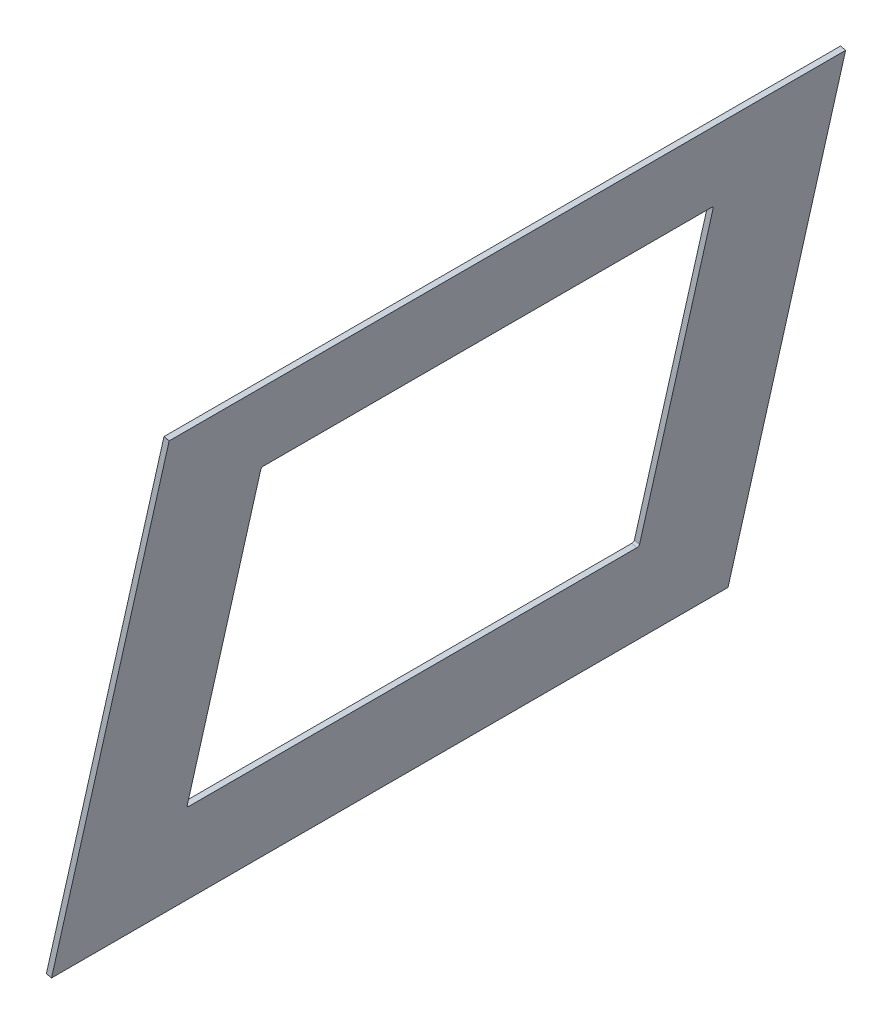
SolidWorks part; units mm, degrees
material "Pine"
ref_plane "Front Plane" through (0, 0, 0) normal (0, 0, 1) x (1, 0, 0)
ref_plane "Top Plane" through (0, 0, 0) normal (0, 1, 0) x (1, 0, 0)
ref_plane "Right Plane" through (0, 0, 0) normal (1, 0, 0) x (0, 0, -1)
sketch "Sketch2" plane through (0, 0, 0) normal (0, 0, 1) x (1, 0, 0)
  line L0 (-108.5345, -3.9032) -> (-108.5345, 1464.0363)
  line L1 (-603.0613, 1609.6249) -> (-744.3883, 980.0776)
  line L2 (-870.5345, -3.9032) -> (-870.5345, 625.8363)
  line L3 (-972.1345, 737.9573) -> (-972.1345, 834.2968)
  line L4 (-768.9345, 834.2968) -> (-768.9345, 986.6968)
  line L5 (-972.1345, 834.2968) -> (-768.9345, 834.2968)
  line L6 (-528.0858, 1843.9468) -> (-737.1845, 1843.9468)
  line L7 (-968.4148, 728.977) -> (-874.2542, 634.8165)
  line L8 (-737.1845, 1672.0154) -> (-737.1845, 1762.6932)
  line L9 (-520.195, 1875.6968) -> (-756.2345, 1875.6968)
  line L10 (-112.2542, 1473.0165) -> (-511.2148, 1871.977)
  line L11 (-737.1845, 1692.941) -> (-241.631, 1467.6894)
  line L12 (-596.8655, 1608.234) -> (-738.1925, 978.6867)
  line L13 (-763.9746, 985.3593) -> (-224.4471, 839.8687)
  line L14 (-761.4898, 1669.1128) -> (-638.6318, 1613.2683)
  line L15 (-631.4955, 1598.9249) -> (-768.9345, 986.6968)
  line L16 (-768.9345, 1680.6745) -> (-768.9345, 1862.9968)
  line L17 (-737.1845, 1780.4468) -> (-737.1845, 1843.9468)
  line L18 (-737.1845, 1692.941) -> (-737.1845, 1843.9468) construction
  line L19 (-737.1845, 1692.941) -> (-737.1845, 1762.6932) construction
  line L20 (-838.7845, -3.9032) -> (-838.7845, 834.2968)
  line L21 (-745.0674, 1675.5986) -> (-249.5139, 1450.347) construction
  line L22 (-140.2845, -3.9032) -> (-140.2845, 1456.1455)
  line L23 (-140.2845, 1456.1455) -> (-528.0858, 1843.9468)
  line L24 (-537.8111, 1581.3911) -> (-673.6845, 976.1369)
  line L25 (-768.9345, 966.9663) -> (-229.407, 821.4757)
  line L26 (-737.1845, 1672.0154) -> (-203.7845, 1429.5608)
  line L27 (-528.0858, 1843.9468) -> (-554.3883, 1780.4468)
  line L28 (-140.2845, 1456.1455) -> (-203.7845, 1429.8429)
  line L29 (-775.2845, -3.9032) -> (-775.2845, 834.2968)
  line L30 (-773.8944, 968.3038) -> (-229.407, 821.4757) construction
  line L31 (-203.7845, -3.9032) -> (-203.7845, 1429.8429)
  line L32 (-203.7845, 1429.8429) -> (-554.3883, 1780.4468)
  line L33 (-554.3883, 1780.4468) -> (-737.1845, 1780.4468)
  line L34 (-768.9345, 966.9663) -> (-763.9746, 985.3593)
  line L35 (-737.1845, 1762.6932) -> (-369.5099, 1595.5683)
  line L36 (-673.6845, 1733.8295) -> (-599.2171, 1699.9807) construction
  line L37 (-737.1845, 1692.941) -> (-625.4936, 1642.1724) construction
  line L38 (-538.5586, 1578.0615) -> (-673.6845, 976.1369) construction
  line L39 (-600.5166, 1591.9704) -> (-737.1845, 983.1768) construction
  line L40 (-554.3883, 1780.4468) -> (-673.6845, 1780.4468) construction
  line L41 (-203.7845, 91.3468) -> (-203.7845, 1429.8429) construction
  line L42 (-140.2845, 27.8468) -> (-140.2845, 1456.1455) construction
  line L43 (-775.2845, 91.3468) -> (-775.2845, 625.8363) construction
  line L44 (-838.7845, 27.8468) -> (-838.7845, 625.8363) construction
  line L45 (-203.7845, 91.3468) -> (-775.2845, 91.3468) construction
  line L46 (-140.2845, 27.8468) -> (-838.7845, 27.8468) construction
  line L47 (-940.3845, 745.8481) -> (-851.8036, 657.2672) construction
  line L48 (-843.7807, 739.0468) -> (-806.9023, 702.1685) construction
  line L49 (-843.7807, 739.0468) -> (-673.6845, 739.0468) construction
  line L50 (-940.3845, 802.5468) -> (-737.1845, 802.5468) construction
  line L51 (-940.3845, 745.8481) -> (-940.3845, 802.5468) construction
  line L52 (-843.7807, 739.0468) -> (-843.7807, 739.0468) construction
  line L53 (-673.6845, 1733.8295) -> (-673.6845, 1780.4468) construction
  line L54 (-756.2345, 1692.941) -> (-756.2345, 1792.2779) construction
  line L55 (-756.2345, 1792.2779) -> (-361.627, 1612.9108) construction
  line L56 (-673.6845, 739.0468) -> (-673.6845, 976.1369) construction
  line L57 (-737.1845, 802.5468) -> (-737.1845, 983.1768) construction
  line L58 (-768.9345, 986.6968) -> (-224.4471, 839.8687) construction
  line L59 (-224.4471, 839.8687) -> (-229.407, 821.4757)
  line L60 (-596.8655, 1608.234) -> (-603.0613, 1609.6249)
  line L61 (-603.0613, 1609.6249) -> (-743.3803, 984.5677) construction
  line L62 (-596.8655, 1608.234) -> (-737.1845, 983.1768) construction
  line L63 (-108.5345, -3.9032) -> (-248.0476, -3.9032)
  line L64 (-744.3883, 980.0776) -> (-738.1925, 978.6867)
  line L68 (-108.5345, -3.9032) -> (-870.5345, -3.9032) construction
  line L69 (-108.5345, -3.9032) -> (-870.5345, -3.9032)
  line L72 (-108.5345, 34.1968) -> (-870.5345, 34.1968)
  arc A0 (-108.5345, 1464.0363) -> (-112.2542, 1473.0165) centre (-121.2345, 1464.0363) ccw
  arc A1 (-511.2148, 1871.977) -> (-520.195, 1875.6968) centre (-520.195, 1862.9968) ccw
  arc A2 (-768.9345, 1862.9968) -> (-756.2345, 1875.6968) centre (-756.2345, 1862.9968) cw
  arc A3 (-768.9345, 1680.6745) -> (-761.4898, 1669.1128) centre (-756.2345, 1680.6745) ccw
  arc A4 (-631.4955, 1598.9249) -> (-638.6318, 1613.2683) centre (-643.8871, 1601.7067) ccw
  arc A5 (-972.1345, 737.9573) -> (-968.4148, 728.977) centre (-959.4345, 737.9573) ccw
  arc A6 (-870.5345, 625.8363) -> (-874.2542, 634.8165) centre (-883.2345, 625.8363) ccw
  arc A7 (-737.1845, 1843.9468) -> (-737.1845, 1843.9468) centre (-737.1845, 1843.9468) cw
  arc A8 (-737.1845, 1692.941) -> (-737.1845, 1692.941) centre (-737.1845, 1692.941) ccw
  arc A12 (-140.2845, 1456.1455) -> (-140.2845, 1456.1455) centre (-140.2845, 1456.1455) ccw
  arc A13 (-528.0858, 1843.9468) -> (-528.0858, 1843.9468) centre (-528.0858, 1843.9468) ccw
  arc A14 (-600.5166, 1591.9704) -> (-625.4936, 1642.1724) centre (-643.8871, 1601.7067) ccw construction
  arc A16 (-203.7845, 1429.8429) -> (-203.7845, 1429.8429) centre (-203.7845, 1429.8429) ccw
  arc A17 (-554.3883, 1780.4468) -> (-554.3883, 1780.4468) centre (-554.3883, 1780.4468) ccw
  arc A18 (-673.6845, 1780.4468) -> (-673.6845, 1780.4468) centre (-673.6845, 1780.4468) cw
  arc A19 (-673.6845, 1733.8295) -> (-673.6845, 1733.8295) centre (-673.6845, 1733.8295) ccw
  arc A20 (-838.7845, 625.8363) -> (-851.8036, 657.2672) centre (-883.2345, 625.8363) ccw construction
  arc A21 (-775.2845, 625.8363) -> (-806.9023, 702.1685) centre (-883.2345, 625.8363) ccw construction
  arc A22 (-843.7807, 739.0468) -> (-843.7807, 739.0468) centre (-843.7807, 739.0468) ccw construction
  arc A23 (-940.3845, 745.8481) -> (-940.3845, 745.8481) centre (-940.3845, 745.8481) ccw construction
  arc A24 (-756.2345, 1692.941) -> (-745.0674, 1675.5986) centre (-737.1845, 1692.941) ccw construction
  dimension "D1" = 12.7
  dimension "D6" = 90
  dimension "D2" = 31.75
  dimension "D3" = 63.5
  dimension "D4" = 19.05
  dimension "D5" = 19.05
  dimension "D8" = 38.1
extrude "Boss-Extrude1" add sketch "Sketch2" along normal blind 812.8 contours L1 L64 L12 L60
sketch "Sketch3" plane through (-918.1356, 206.1121, 0) normal (-0.9757, 0.219, 0) x (0, 0, 1)
  line L10 (134.6454, 922.7681) -> (134.6454, 1326.3423)
  line L11 (678.1546, 922.7681) -> (678.1546, 1326.3423)
  line L14 (137.1854, 1328.8823) -> (675.6146, 1328.8823)
  line L22 (137.1854, 920.2281) -> (675.6146, 920.2281)
  arc A0 (137.1854, 920.2281) -> (134.6454, 922.7681) centre (137.1854, 922.7681) cw
  arc A1 (675.6146, 920.2281) -> (678.1546, 922.7681) centre (675.6146, 922.7681) ccw
  arc A2 (678.1546, 1326.3423) -> (675.6146, 1328.8823) centre (675.6146, 1326.3423) ccw
  arc A3 (134.6454, 1326.3423) -> (137.1854, 1328.8823) centre (137.1854, 1326.3423) cw
  dimension "D1" = 2.54
extrude "Cut-Extrude1" cut sketch "Sketch3" against normal blind 6.35
